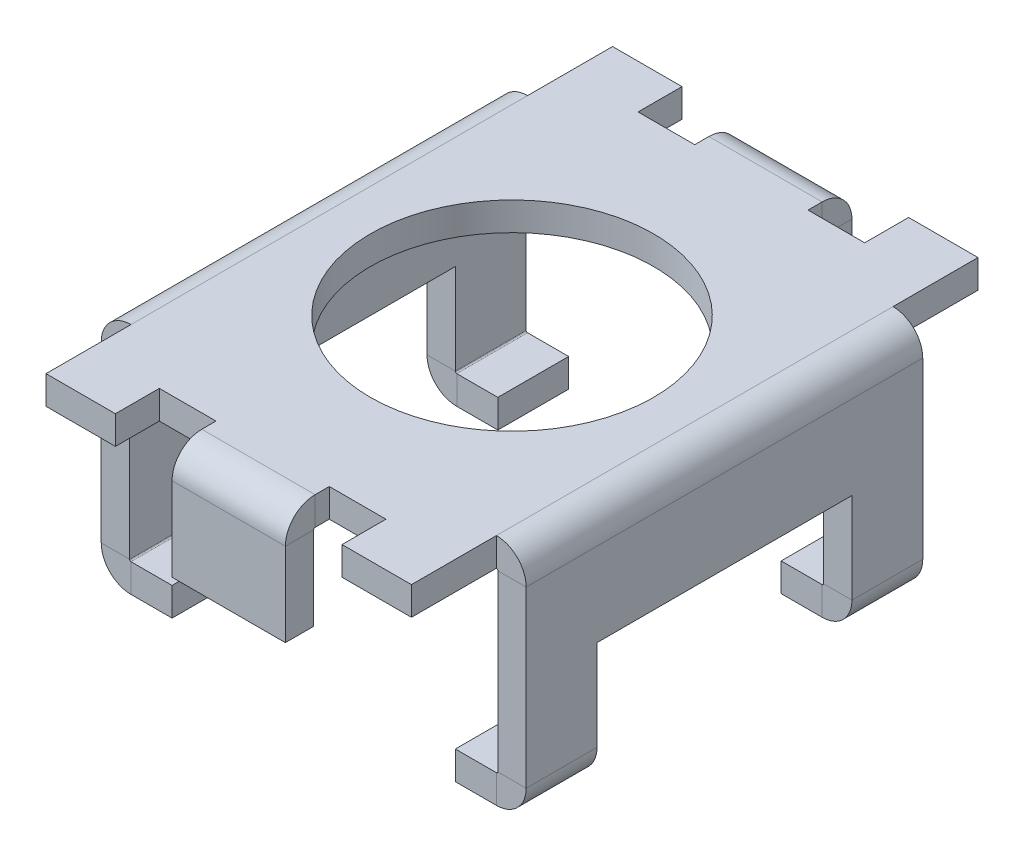
SolidWorks part; units mm, degrees
note: The reader was unsure of these and kept them because the rebuilt part matched: flange length of "Edge-Flange1", "Edge-Flange2", "Edge-Flange3".
material "普通碳钢"
ref_plane "Front Plane" through (0, 0, 0) normal (0, 0, 1) x (1, 0, 0)
ref_plane "Top Plane" through (0, 0, 0) normal (0, 1, 0) x (1, 0, 0)
ref_plane "Right Plane" through (0, 0, 0) normal (1, 0, 0) x (0, 0, -1)
sketch "Sketch1" plane through (0, 0, 0) normal (0, 1, 0) x (1, 0, 0)
  line L0 (-55, 0) -> (55, 0) construction
  line L1 (-1.5, 2) -> (1.5, 2)
  line L2 (-1.5, 2) -> (-1.5, -2)
  line L3 (-1.5, -2) -> (1.5, -2)
  line L4 (1.5, 2) -> (1.5, -2)
  line L5 (0, -55) -> (0, 55) construction
  dimension "D1" = 4
  dimension "D2" = 2
  dimension "D3" = 3
  dimension "D4" = 1.5
sheet metal parameters "Sheet-Metal1" thickness 0.2 parameters "D1"=1.905
base flange "Base-Flange1" sketch "Sketch1" thickness 0.2 reverse thickness direction no parameters "D1"=1.905
edge flange "Edge-Flange1" sketch "Sketch6" flange profiles "Sketch6", "Sketch8" flange angle 90 flange length 0.8 flange position material inside bend radius 0.01 thickness 0.2 parameters "D6"=10, "D8"=1
sketch "Sketch6" plane through (0, -0.2, 2) normal (0, 0, 1) x (-1, 0, 0)
  line L0 (1.5, 0) -> (-1.5, 0) construction
  line L1 (0.4, 0) -> (-0.4, 0)
  line L2 (-0.4, 0) -> (-0.4, 0.6)
  line L3 (-0.4, 0.6) -> (0.4, 0.6)
  line L4 (0.4, 0.6) -> (0.4, 0)
  line L5 (0, -0.09) -> (0, -0.31) construction
  dimension "D1" = 0.4
  dimension "D2" = 0.8
sketch "Sketch8" plane through (0, -0.2, -2) normal (0, 0, -1) x (1, 0, 0)
  line L0 (1.5, 0) -> (-1.5, 0) construction
  line L1 (0.4, 0) -> (-0.4, 0)
  line L2 (-0.4, 0) -> (-0.4, 0.6)
  line L3 (-0.4, 0.6) -> (0.4, 0.6)
  line L4 (0.4, 0.6) -> (0.4, 0)
  line L6 (0.4, 0) -> (0.4, 0.6) construction
  line L8 (-0.4, 0.6) -> (-0.4, 0) construction
bend "EdgeBend1" bend radius 0.01 bend angle 90 parameters "D5"=1
bend "EdgeBend2" bend radius 0.01 bend angle 90 parameters "D5"=2
edge flange "Edge-Flange2" sketch "Sketch13" flange profiles "Sketch13", "Sketch14" flange angle 90 flange length 1.65 flange position material inside bend radius 0.01 thickness 0.2 parameters "D6"=10, "D8"=1
sketch "Sketch13" plane through (-1.5, -0.2, 0) normal (-1, 0, 0) x (0, 0, -1)
  line L0 (2, 0) -> (-2, 0) construction
  line L1 (1.4, 0) -> (-1.4, 0)
  line L2 (-1.4, 0) -> (-1.4, 1.45)
  line L3 (-1.4, 1.45) -> (1.4, 1.45)
  line L4 (1.4, 1.45) -> (1.4, 0)
  line L5 (0, 0.24) -> (0, -0.64) construction
  dimension "D1" = 1.4
  dimension "D2" = 2.8
sketch "Sketch14" plane through (1.5, -0.2, 0) normal (1, 0, 0) x (0, 0, 1)
  line L0 (2, 0) -> (-2, 0) construction
  line L1 (1.4, 0) -> (-1.4, 0)
  line L2 (-1.4, 0) -> (-1.4, 1.45)
  line L3 (-1.4, 1.45) -> (1.4, 1.45)
  line L4 (1.4, 1.45) -> (1.4, 0)
  line L5 (1.4, 0) -> (1.4, 1.45) construction
  line L6 (-1.4, 1.45) -> (-1.4, 0) construction
bend "EdgeBend3" bend radius 0.01 bend angle 90 parameters "D5"=3
bend "EdgeBend4" bend radius 0.01 bend angle 90 parameters "D5"=4
edge flange "Edge-Flange3" sketch "Sketch21" flange profiles "Sketch21", "Sketch22" flange angle 90 flange length 0.5 flange position material inside bend radius 0.01 thickness 0.2 parameters "D6"=10, "D8"=1
sketch "Sketch21" plane through (-1.3, -1.65, 0) normal (0, -1, 0) x (0, 0, -1)
  line L0 (1.4, 0) -> (-1.4, 0) construction
  line L1 (1.4, 0) -> (-1.4, 0)
  line L2 (-1.4, 0) -> (-1.4, 0.3)
  line L3 (-1.4, 0.3) -> (1.4, 0.3)
  line L4 (1.4, 0.3) -> (1.4, 0)
sketch "Sketch22" plane through (1.3, -1.65, 0) normal (0, -1, 0) x (0, 0, 1)
  line L0 (1.4, 0) -> (-1.4, 0) construction
  line L1 (1.4, 0) -> (-1.4, 0)
  line L2 (-1.4, 0) -> (-1.4, 0.3)
  line L3 (-1.4, 0.3) -> (1.4, 0.3)
  line L4 (1.4, 0.3) -> (1.4, 0)
bend "EdgeBend5" bend radius 0.01 bend angle 90 parameters "D5"=5
bend "EdgeBend6" bend radius 0.01 bend angle 90 parameters "D5"=6
sketch "Sketch23" plane through (0, 0, 0) normal (1, 0, 0) x (0, 0, -1)
  line L0 (-1.4, -1.65) -> (1.4, -1.65) construction
  line L1 (-0.9, -0.8) -> (0.9, -0.8)
  line L2 (-0.9, -0.8) -> (-0.9, -1.65)
  line L3 (-0.9, -1.65) -> (0.9, -1.65)
  line L4 (0.9, -0.8) -> (0.9, -1.65)
  line L5 (0, 0.9075) -> (0, -0.9075) construction
  line L6 (1.65, 0) -> (-1.65, 0) construction
  line L7 (-1.4, -0.21) -> (-1.4, -1.44) construction
  dimension "D1" = 1.8
  dimension "D2" = 0.9
  dimension "D3" = 0.8
  dimension "D4" = 0.5
extrude "Cut-Extrude1" cut sketch "Sketch23" against normal blind 10 and the other way blind 10
sketch "Sketch24" plane through (0, 0, 0) normal (0, 1, 0) x (1, 0, 0)
  circle A0 centre (0, 0) radius 1
  dimension "D1" = 2
extrude "Cut-Extrude2" cut sketch "Sketch24" against normal blind 10
flat pattern "Flat-Pattern1" [suppressed]
sketch "Bend-Lines1" plane through (0, 0, 0) normal (0, 1, 0) x (1, 0, 0)
sketch3d "Bounding-Box1" [suppressed]
  line L0 (1.75, 2.35, 0) -> (1.75, -2.35, 0) construction
  line L1 (-1.75, 2.35, 0) -> (-1.75, -2.35, 0) construction
  line L2 (1.75, 2.35, 0) -> (-1.75, 2.35, 0) construction
  line L3 (1.75, -2.35, 0) -> (-1.75, -2.35, 0) construction
bend of the flat pattern "Flatten-<EdgeBend1>1"
bend of the flat pattern "Flatten-<EdgeBend2>1"
bend of the flat pattern "Flatten-<EdgeBend3>1"
bend of the flat pattern "Flatten-<EdgeBend4>1"
bend of the flat pattern "Flatten-<EdgeBend5>1"
bend of the flat pattern "Flatten-<EdgeBend6>1"
